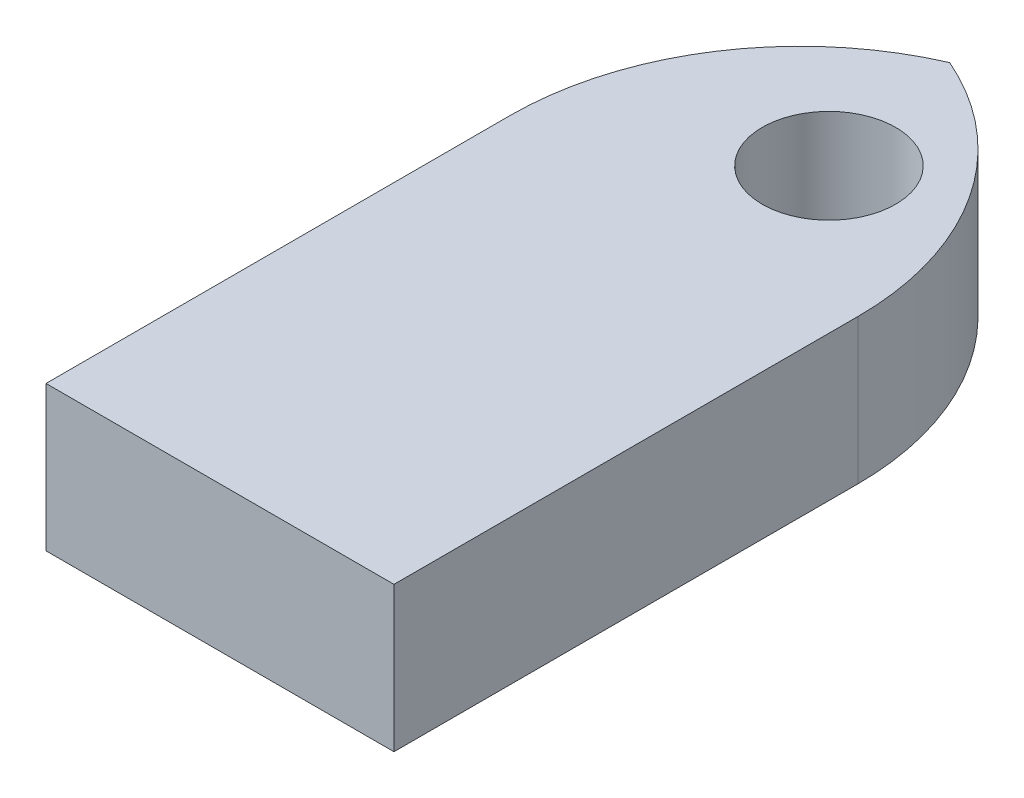
SolidWorks part; units mm, degrees
ref_plane "Front Plane" through (0, 0, 0) normal (0, 0, 1) x (1, 0, 0)
ref_plane "Top Plane" through (0, 0, 0) normal (0, 1, 0) x (1, 0, 0)
ref_plane "Right Plane" through (0, 0, 0) normal (1, 0, 0) x (0, 0, -1)
sketch "Sketch1" plane through (0, 0, 0) normal (0, 1, 0) x (1, 0, 0)
  line L1 (0, 0) -> (7.62, 0)
  line L2 (0, 0) -> (0, 16.51)
  line L3 (0, 16.51) -> (7.62, 16.51)
  line L4 (7.62, 0) -> (7.62, 16.51)
  circle A0 centre (4.445, 12.7) radius 1.4605
  dimension "D3" = 2.921
  dimension "D1" = 7.62
  dimension "D2" = 16.51
  dimension "D4" = 3.81
  dimension "D5" = 4.445
extrude "Boss-Extrude1" add sketch "Sketch1" along normal blind 3.175
fillet "Fillet3" radius 6.35 2 edges at (0, 1.5875, -16.51) (7.62, 1.5875, -16.51)
